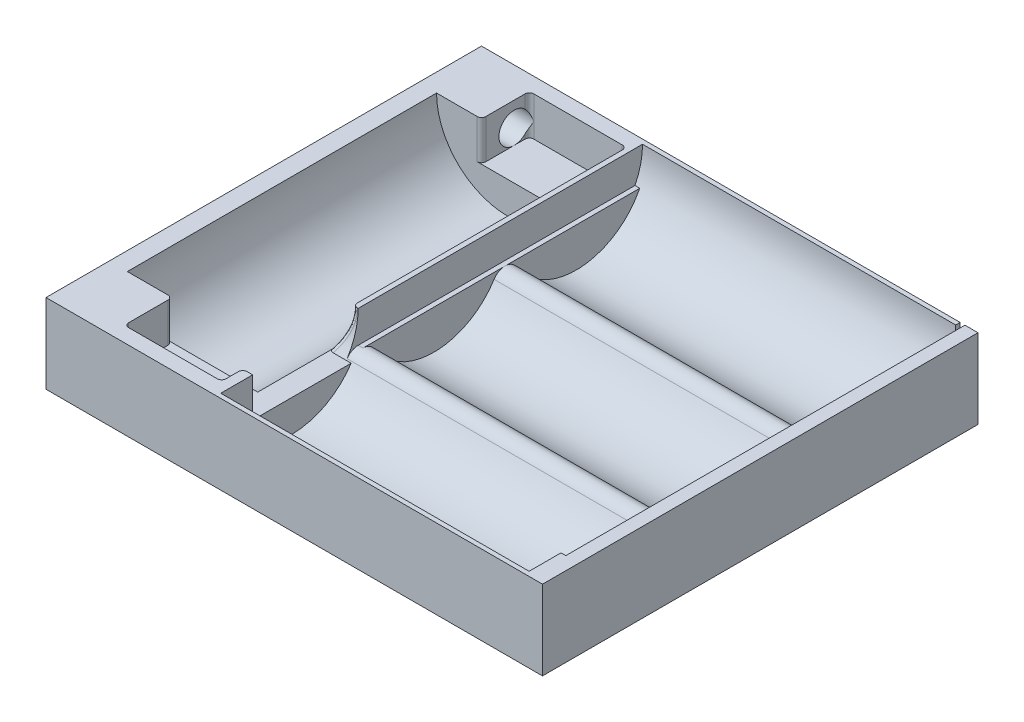
SolidWorks part; units mm, degrees
ref_plane "Front Plane" through (0, 0, 0) normal (0, 0, 1) x (1, 0, 0)
ref_plane "Top Plane" through (0, 0, 0) normal (0, 1, 0) x (1, 0, 0)
ref_plane "Right Plane" through (0, 0, 0) normal (1, 0, 0) x (0, 0, -1)
sketch "Sketch1" plane through (0, 0, 0) normal (0, 1, 0) x (1, 0, 0)
  line L1 (-57, 50) -> (57, 50)
  line L2 (-57, 50) -> (-57, -50)
  line L3 (-57, -50) -> (57, -50)
  line L4 (57, 50) -> (57, -50)
  line L5 (-57, 50) -> (57, -50) construction
  line L6 (-57, -50) -> (57, 50) construction
  point P0 (0, 0)
  dimension "D1" = 100
  dimension "D2" = 114
extrude "Boss-Extrude1" add sketch "Sketch1" along normal blind 18.25
ref_plane "Plane1" through (54, 0, 0) normal (1, 0, 0) x (0, 0, -1)
sketch "Sketch2" plane through (54, 0, 0) normal (1, 0, 0) x (0, 0, -1)
  line L0 (-50, 18.25) -> (50, 18.25) construction
  line L1 (0, 0) -> (0, -18.713) construction
  circle A0 centre (0, 18.25) radius 16.325
  circle A1 centre (32.65, 18.25) radius 16.325
  circle A2 centre (-32.65, 18.25) radius 16.325
  dimension "D1" = 32.65
  dimension "D2" = 32.65
extrude "Cut-Extrude1" cut sketch "Sketch2" against normal blind 73 contours A0 | A2 | A1
fillet "Fillet1" radius 3 2 edges at (17.5, 18.25, -16.325) (17.5, 18.25, 16.325)
sketch "Sketch3" plane through (0, 0, 0) normal (0, 0, 1) x (1, 0, 0)
  line L0 (57, 18.25) -> (-57, 18.25) construction
  circle A0 centre (-36.5, 18.25) radius 16.325
  point P2 (0, 0)
  dimension "D1" = 32.65
  dimension "D2" = 36.5
extrude "Cut-Extrude2" cut sketch "Sketch3" against normal blind 35.5 and the other way blind 35.5
sketch "Sketch4" plane through (0, 0, -35.5) normal (0, 0, 1) x (1, 0, 0)
  line L0 (-42.5, 18.25) -> (-42.5, 9.25)
  line L1 (-52.825, 18.25) -> (-20.175, 18.25) construction
  line L2 (-42.5, 18.25) -> (-20.175, 18.25)
  line L3 (-42.5, 9.25) -> (-22.88, 9.25)
  arc A0 (-52.825, 18.25) -> (-20.175, 18.25) centre (-36.5, 18.25) ccw construction
  arc A1 (-22.88, 9.25) -> (-20.175, 18.25) centre (-36.5, 18.25) ccw
  dimension "D1" = 9
  dimension "D2" = 6
extrude "Cut-Extrude3" cut sketch "Sketch4" against normal blind 11
mirror "Mirror1" about plane through (0, 0, 0) normal (0, 0, 1) of "Cut-Extrude3"
sketch "Sketch5" plane through (-19, 0, 0) normal (1, 0, 0) x (0, 0, -1)
  line L0 (-41.65, 18.25) -> (-41.65, 9.25)
  line L1 (-48.975, 18.25) -> (-16.325, 18.25) construction
  line L2 (-41.65, 9.25) -> (-19.03, 9.25)
  line L3 (-46.5, 9.25) -> (-35.5, 9.25) construction
  line L4 (-41.65, 18.25) -> (-16.325, 18.25)
  line L5 (-16.325, 18.25) -> (16.325, 18.25) construction
  arc A0 (-48.975, 18.25) -> (-18.8593, 9.5138) centre (-32.65, 18.25) ccw construction
  arc A1 (-19.03, 9.25) -> (-18.8593, 9.5138) centre (-32.65, 18.25) ccw
  arc A2 (-18.8593, 9.5138) -> (-16.325, 18.25) centre (-32.65, 18.25) ccw
  point P12 (-16.4, 18.25)
  point P15 (-16.5442, 18.25)
  dimension "D1" = 9
extrude "Cut-Extrude4" cut sketch "Sketch5" against normal blind 10
fillet "Fillet3" radius 1 8 edges at (-20.8659, 13.5511, 17.0159) (-20.8659, 13.5511, 41.65) (-20.8659, 13.5511, -46.5) (-42.5, 13.75, -46.5) (-42.5, 13.75, -35.5) (-42.5, 13.75, 35.5) (-42.5, 13.75, 46.5) (-20.8659, 13.5511, 46.5)
sketch "Sketch6" plane through (-42.5, 0, 0) normal (1, 0, 0) x (0, 0, -1)
  line L1 (45.5, 9.25) -> (35.5, 9.25) construction
  line L2 (46.5, 18.25) -> (46.5, 9.25) construction
  circle A0 centre (43, 12.75) radius 3.5
  point P2 (41.6011, 12.8999)
  point P5 (41.935, 12.25)
  point P7 (41.1365, 15.719)
  dimension "D1" = 7
extrude "Cut-Extrude6" cut sketch "Sketch6" against normal through all and the other way blind 1
sketch "Sketch7" plane through (-19, 0, 0) normal (1, 0, 0) x (0, 0, -1)
  line L0 (47.231, 10.9083) -> (-16.325, 10.9083)
  arc A0 (18.8593, 9.5138) -> (48.975, 18.25) centre (32.65, 18.25) ccw construction
  arc A1 (18.8593, 9.5138) -> (13.7907, 9.5138) centre (16.325, 7.9083) ccw construction
  arc A2 (-13.7907, 9.5138) -> (13.7907, 9.5138) centre (0, 18.25) ccw construction
  arc A3 (18.8593, 9.5138) -> (47.231, 10.9083) centre (32.65, 18.25) ccw
  arc A4 (18.8593, 9.5138) -> (13.7907, 9.5138) centre (16.325, 7.9083) ccw
  arc A5 (-13.7907, 9.5138) -> (13.7907, 9.5138) centre (0, 18.25) ccw
  arc A6 (-13.7907, 9.5138) -> (-18.8593, 9.5138) centre (-16.325, 7.9083) ccw construction
  arc A7 (-13.7907, 9.5138) -> (-16.325, 10.9083) centre (-16.325, 7.9083) ccw
  point P8 (-16.4, 10.8866)
  point P9 (-11.2953, 14.7072)
  point P10 (0, 0)
  point P11 (0, 0)
  point P14 (-14.654, 10.8866)
  point P16 (-16.4, 10.8866)
  arc M4 (-18.8593, 9.5138) -> (-13.7907, 9.5138) centre (-16.325, 7.9083) cw
  arc M5 (-13.7907, 9.5138) -> (13.7907, 9.5138) centre (0, 18.25) ccw
  arc M6 (13.7907, 9.5138) -> (18.8593, 9.5138) centre (16.325, 7.9083) cw
  arc M7 (18.8593, 9.5138) -> (48.975, 18.25) centre (32.65, 18.25) ccw
extrude "Boss-Extrude2" add sketch "Sketch7" along normal blind 1.1 contours L0 M7 M6 | L0 M6 M4 M5
ref_plane "Plane2" through (17.5, 0, 0) normal (1, 0, 0) x (0, 0, -1)
mirror "Mirror2" about plane through (17.5, 0, 0) normal (1, 0, 0) of "Boss-Extrude2"
sketch "Sketch8" plane through (-19, 0, 0) normal (1, 0, 0) x (0, 0, -1)
  line L3 (-19.03, 9.25) -> (-41.65, 9.25)
  line L4 (-41.65, 9.25) -> (-41.65, 18.25)
  line L5 (-41.65, 9.25) -> (-41.65, 18.25)
  line L6 (-19.03, 9.25) -> (-41.65, 9.25)
  line L9 (-41.65, 18.25) -> (-48.975, 18.25)
  line L12 (-41.65, 18.25) -> (-48.975, 18.25)
  arc A1 (-48.975, 18.25) -> (-19.03, 9.25) centre (-32.65, 18.25) ccw
  arc A2 (-48.975, 18.25) -> (-19.03, 9.25) centre (-32.65, 18.25) ccw
  dimension "D1" = 0
extrude "Boss-Extrude3" add sketch "Sketch8" along normal up to surface (1.1 mm away) up to face at (-17.9, 8.4767, 0)
mirror "Mirror3" about plane through (17.5, 0, 0) normal (1, 0, 0) of "Boss-Extrude3"
sketch "Sketch10" plane through (0, 18.25, 0) normal (0, 1, 0) x (1, 0, 0)
  line L0 (54, -10.0375) -> (54, 10.0375) construction
  line L1 (52.9, 47.231) -> (54, 47.231)
  line L2 (52.9, 47.231) -> (52.9, 56.7433)
  line L3 (52.9, 56.7433) -> (54, 56.7433)
  line L4 (54, 47.231) -> (54, 56.7433)
extrude "Cut-Extrude9" cut sketch "Sketch10" against normal blind 6
